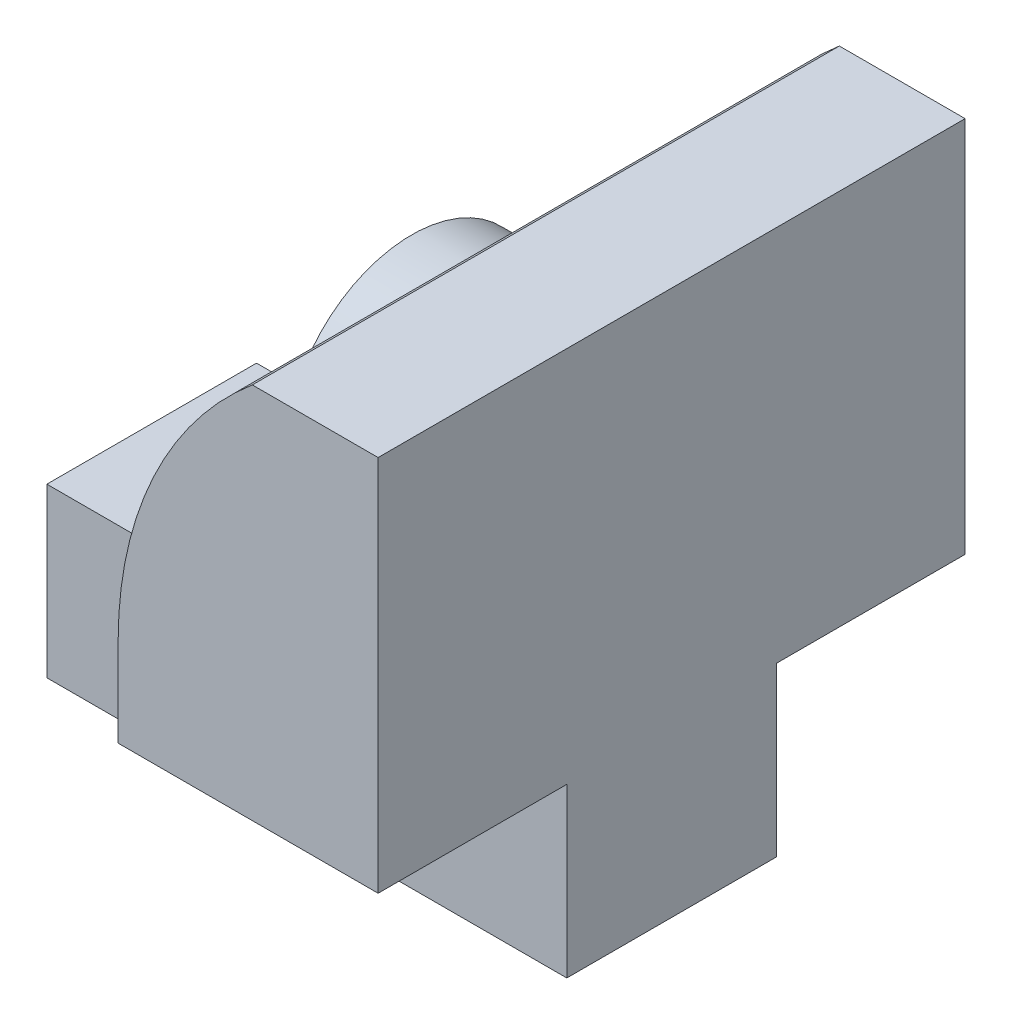
SolidWorks part; units mm, degrees
material "Malleable Cast Iron"
ref_plane "Front Plane" through (0, 0, 0) normal (0, 0, 1) x (1, 0, 0)
ref_plane "Top Plane" through (0, 0, 0) normal (0, 1, 0) x (1, 0, 0)
ref_plane "Right Plane" through (0, 0, 0) normal (1, 0, 0) x (0, 0, -1)
sketch "Sketch1" plane through (0, 0, 0) normal (0, 0, 1) x (1, 0, 0)
  line L0 (0, 0) -> (-25, 0)
  line L1 (-25, 0) -> (-25, -20)
  line L2 (-25, -20) -> (37, -20)
  line L3 (37, -20) -> (37, 0)
  line L4 (37, 0) -> (0, 0)
  dimension "D1" = 62
  dimension "D2" = 20
  dimension "D3" = 37
extrude "Boss-Extrude1" add sketch "Sketch1" along normal mid plane 25
sketch "Sketch2" plane through (0, 0, 0) normal (0, 0, 1) x (1, 0, 0)
  line L0 (6, 0) -> (6, 10.5907)
  line L1 (37, 0) -> (-25, 0) construction
  line L2 (22, 45) -> (37, 45)
  line L3 (37, 45) -> (37, 0)
  line L4 (6, 0) -> (37, 0)
  arc A0 (6, 10.5907) -> (22, 45) centre (51, 10.5907) cw
  dimension "D3" = 45
  dimension "D1" = 45
  dimension "D2" = 15
extrude "Boss-Extrude2" add sketch "Sketch2" along normal mid plane 70
sketch "Sketch3" plane through (0, -20, 0) normal (0, -1, 0) x (1, 0, 0)
  line L0 (37, 12.5) -> (37, -12.5) construction
  line L1 (-25, 12.5) -> (-25, -12.5) construction
  point P0 (25, 0)
  point P1 (-13, 0)
  dimension "D1" = 12
  dimension "D2" = 12
sketch "Sketch4" plane through (6, 0, 0) normal (-1, 0, 0) x (0, 0, 1)
  line L0 (12.5, -20) -> (-12.5, -20) construction
  line L1 (15, 20) -> (15, 0)
  line L2 (-15, 20) -> (-15, 0)
  line L3 (-12.5, 0) -> (-35, 0) construction
  arc A0 (15, 20) -> (-15, 20) centre (0, 20) ccw
  circle A1 centre (0, 20) radius 9
  circle A2 centre (0, 20) radius 6
  circle A3 centre (0, 20) radius 11
  line M3 (-35, 0) -> (-12.5, 0)
  line M4 (-12.5, 0) -> (12.5, 0)
  line M5 (12.5, 0) -> (35, 0)
  line M7 (35, 10.5907) -> (-35, 10.5907)
  dimension "D2" = 30
  dimension "D3" = 18
  dimension "D4" = 12
  dimension "D5" = 22
  dimension "D1" = 40
extrude "Boss-Extrude3" add sketch "Sketch4" against normal up to next contours A3 L2 L1 M7 M3 M4 M5 | A3 L1 A0 L2 M7 | A3 A1 M7 | A3 M7 | A1 A2 | A2 region at (6, 15.2953, 14.6132) region at (6, 5.1083, 0) region at (6, 10.8908, 0) region at (6, 9.9503, 0) region at (6, 20, -8.7454) region at (6, 20, 0)
extrude "Cut-Extrude1" cut sketch "Sketch4<3>" against normal blind 10 contours A3 A1 M7 | A3 M7 | A1 A2 | A2 region at (6, 10.8908, 0) region at (6, 9.9503, 0) region at (6, 20, -8.7454) region at (6, 20, 0)
sketch "Sketch4<3>" plane through (6, 0, 0) normal (-1, 0, 0) x (0, 0, 1) same geometry as "Sketch4"
extrude "Cut-Extrude2" cut sketch "Sketch4<4>" against normal blind 12 from surface contours A1 A2 | A2 region at (6, 20, -8.7454) region at (6, 20, 0) starting at face at (16, 20, 11)
sketch "Sketch4<4>" plane through (6, 0, 0) normal (-1, 0, 0) x (0, 0, 1) same geometry as "Sketch4"
extrude "Cut-Extrude4" cut sketch "Sketch4<5>" against normal blind 6 from surface contours A2 region at (6, 20, 0) starting at face at (28, 20, 9)
sketch "Sketch4<5>" plane through (6, 0, 0) normal (-1, 0, 0) x (0, 0, 1) same geometry as "Sketch4"
hole_wizard "Ø8.0mm Dowel Hole1" positions "Sketch5" profile "Sketch6" hole size "Ø8.0" standard "ANSI Metric"
sketch "Sketch5" plane through (0, -20, 0) normal (0, -1, 0) x (-1, 0, 0)
  point P0 (-25, 0)
  point P3 (13, 0)
sketch "Sketch6" plane through (25, -20, 0) normal (1, 0, 0) x (0, 0, -1)
  line L0 (0, 0) -> (0, 19.4034)
  line L1 (0, 19.4034) -> (4, 17)
  line L2 (4, 17) -> (4, 0)
  line L5 (4, 0) -> (0, 0)
  line L10 (0, 19.4034) -> (-4, 17) construction
  line L11 (0, -6.35) -> (0, 107.95) construction
  dimension "Hole Dia." = 8
  dimension "Hole Depth" = 17
  dimension "Drill Angle" = 118
thread "Thread1" pitch 2 method cut trim with start face yes trim with end face yes profile "Thread Profile1" start angle 0, offset 1, length 0, pitch 2, diameter 22
ref_plane "Plane1" through (5, 20, -11) normal (0, -1, 0) x (0, 0, -1)
sketch "Thread Profile1" plane through (5, 20, -11) normal (0, -1, 0) x (0, 0, -1)
  line L0 (0, 0) -> (0, 2) construction
  line L1 (0, 0) -> (1.0825, 0.625)
  line L2 (1.0825, 0.625) -> (1.0825, 0.875)
  line L3 (1.0825, 0.875) -> (0, 1.5)
  line L4 (1.0825, 0.75) -> (0, 0.75) construction
  line L11 (0, 0) -> (0, 1.5)
  point P2 (0, 0)
  dimension "Pitch" = 2
  dimension "Profile_Angle" = 60
  dimension "Profile_Land" = 0.25
  dimension "Profile_Height" = 1.0825
